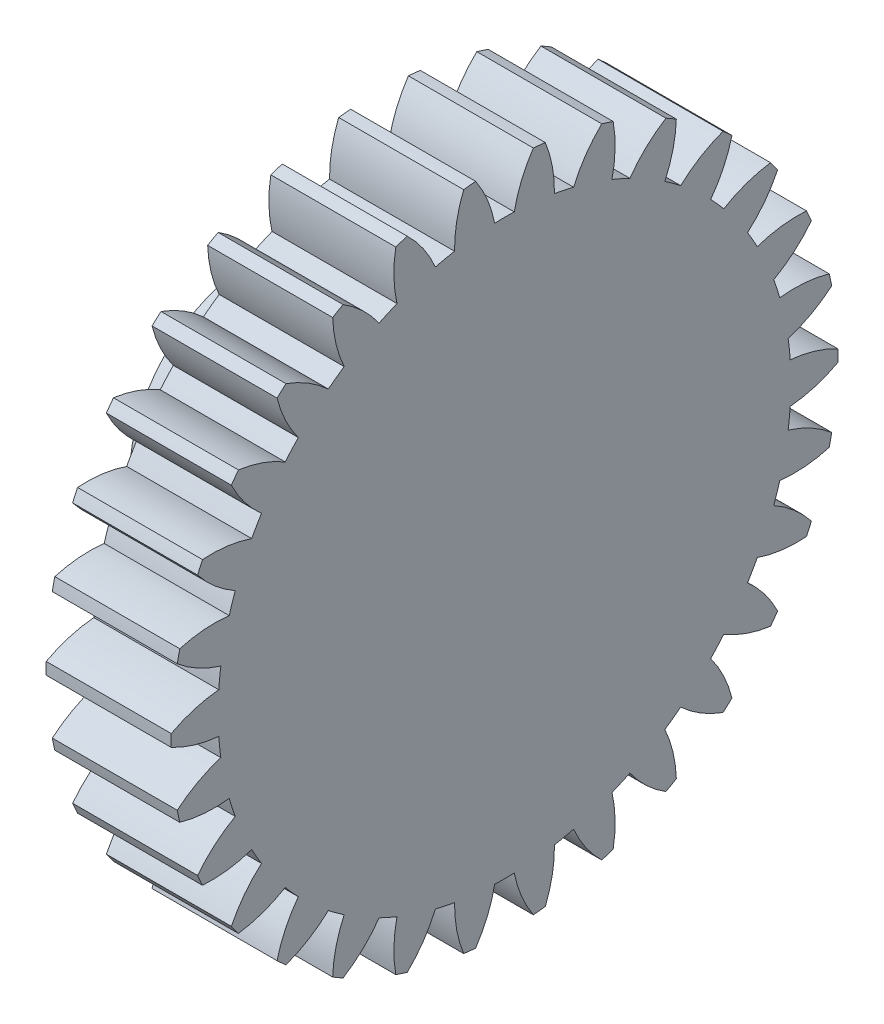
SolidWorks part; units mm, degrees
ref_plane "Plane1" through (0, 0, 0) normal (0, 0, 1) x (1, 0, 0)
ref_plane "Plane2" through (0, 0, 0) normal (0, 1, 0) x (1, 0, 0)
ref_plane "Plane3" through (0, 0, 0) normal (1, 0, 0) x (0, 0, -1)
other "Configuration Table"
sketch "HoldingSke" plane through (0, 0, 0) normal (0, 1, 0) x (1, 0, 0)
  line L0 (0, 0) -> (263.9645, -152.4)
  line L1 (-15, 0) -> (100, 0) construction
  line L2 (0, 0) -> (-2.1039, 2.3779)
  line L3 (0, 0) -> (-11.863, 4.5341)
  line L4 (0, 0) -> (7.479, 4.318)
  line L5 (0, 0) -> (-47.5972, -17.7524)
  line L6 (0, 0) -> (-10.5278, -7.1032)
  line L7 (-2.1039, 2.3779) -> (8.831, 51.988)
  line L8 (-76.2, 54.61) -> (-54.9402, 54.61)
  line L9 (-71.009, 38.7566) -> (-53.1078, 45.2721)
  line L10 (-76.2, 71.12) -> (104.1128, 71.12)
  line L11 (0, 0) -> (-12.7, 0)
  line L12 (-76.2, 101.6) -> (-76.1147, 101.6)
  line L13 (24.9733, 27.94) -> (52.9518, 28.4284)
  line L14 (24.9733, 27.94) -> (24.9746, 27.94)
  line L15 (24.9733, 27.94) -> (100.4006, 29.5858)
  circle A0 centre (0, 0) radius 9.525
  circle A1 centre (0, 0) radius 29.1029
  circle A2 centre (0, 0) radius 38.1
  circle A3 centre (0, 0) radius 9.525
  dimension "MHD" = 58.2058
  dimension "Hub_dia" = 76.2
  dimension "Bore" = 19.05
  dimension "MBD" = 19.05
  dimension "Num_teeth" = 30
  dimension "Pitch" = 304.8
  dimension "Overall_len" = 50.8
  dimension "Show_teeth" = 30
  dimension "Thickness" = 12.7
  dimension "OAL" = 50.801
  dimension "T_dim" = 21.2598
  dimension "Ap" = 20
  dimension "H" = 19.05
  dimension "Pitch_radius" = 180.3128
  dimension "Width" = 12.7
  dimension "Backlash" = 0.0853
  dimension "Addendum_fac" = 1
  dimension "Dedendum_fac" = 1.25
  dimension "Clearance_fac" = 0.25
  dimension "Dedendum_add" = 0.0013
sketch "BasProSke" plane through (0, 0, 0) normal (0, 1, 0) x (1, 0, 0)
  line L0 (-10, 0) -> (60, 0) construction
  line L1 (0, 0) -> (0, 33.8667)
  line L2 (0, 0) -> (12.7, 0)
  line L3 (12.7, 0) -> (12.7, 33.8667)
  line L4 (12.7, 33.8667) -> (0, 33.8667)
  dimension "Thickness" = 12.7
  dimension "Diameter" = 67.7333
revolve "Base-Revolve" add sketch "BasProSke" angle 360 about L0
sketch "TooCutSke" plane through (0, 0, 0) normal (1, 0, 0) x (0, 0, -1)
  line L1 (0, 0) -> (0, 107) construction
  line L2 (0, 0) -> (-1.811, 31.6983) construction
  line L3 (0, 0) -> (-6.63, 63.0805) construction
  line L4 (-1.811, 31.6983) -> (-3.315, 31.5402) construction
  arc A0 (0.9953, 29.0859) -> (-0.9953, 29.0859) centre (0, 0) ccw
  arc A1 (2.9488, 33.7635) -> (-2.9488, 33.7635) centre (0, 0) ccw
  circle A2 centre (0, 0) radius 31.75 construction
  circle A3 centre (0, 0) radius 29.8352 construction
  arc A4 (-0.9953, 29.0859) -> (-2.9488, 33.7635) centre (-13.4553, 26.6289) ccw
  arc A5 (2.9488, 33.7635) -> (0.9953, 29.0859) centre (13.4553, 26.6289) ccw
  dimension "Root_dia" = 58.2058
  dimension "Overcut_dia" = 67.7841
  dimension "Pitch_dia" = 63.5
  dimension "Base_dia" = 59.6705
  dimension "Flank_rad" = 12.7
  dimension "Half_ang" = 6
  dimension "Half_CT" = 1.5123
extrude "ToothCut" cut sketch "TooCutSke" along normal through all
fillet "Breaks" [suppressed] radius 0.0423 tangent propagation no
fillet "RootFillets" [suppressed] radius 0.5304
pattern_circular "TeethCuts" count 30 every 12 about axis through (-10, 0, 0) along (1, 0, 0) of "ToothCut", "RootFillets", "Breaks"
sketch "HubNeaOneSke" plane through (0, 0, 0) normal (-1, 0, 0) x (0, 0, 1)
  circle A0 centre (0, 0) radius 29.1029
  dimension "Diameter" = 58.2058
extrude "HubNearOne" [suppressed] add sketch "HubNeaOneSke" along normal blind 38.101
sketch "HubNeaBotSke" plane through (0, 0, 0) normal (-1, 0, 0) x (0, 0, 1)
  circle A0 centre (0, 0) radius 29.1029
  dimension "Diameter" = 58.2058
extrude "HubNearBoth" [suppressed] add sketch "HubNeaBotSke" along normal blind 19.0505
ref_plane "FarPln" through (12.7, 0, 0) normal (1, 0, 0) x (0, 0, -1)
sketch "HubFarSke" plane through (12.7, 0, 0) normal (1, 0, 0) x (0, 0, -1)
  circle A0 centre (0, 0) radius 29.1029
  dimension "Diameter" = 58.2058
extrude "HubFar" [suppressed] add sketch "HubFarSke" along normal blind 19.0505
sketch "Sketch1" plane through (0, 0, 0) normal (-1, 0, 0) x (0, 0, 1)
  circle A0 centre (0, 0) radius 12.7
  circle A1 centre (0, 0) radius 4.953
  dimension "D1" = 9.906
  dimension "D2" = 25.4
extrude "Boss-Extrude2" add sketch "Sketch1" along normal blind 12.7
sketch "Sketch3" plane through (0, 0, 0) normal (0, 1, 0) x (1, 0, 0)
  line L0 (0, 0.9953) -> (0, -0.9953) construction
  line L2 (-12.7, 0) -> (0, 0) construction
  circle A0 centre (-6.35, 0) radius 3.302
  point P4 (0, 0)
  point P7 (0, 0)
  dimension "D1" = 6.604
  dimension "D2" = 6.35
extrude "Cut-Extrude1" cut sketch "Sketch3" along normal through all
sketch "Sketch4" plane through (0, 0, 0) normal (0, 1, 0) x (1, 0, 0)
  line L1 (-3.527, 4.8895) -> (-9.173, 4.8895)
  line L2 (-9.173, 4.8895) -> (-11.9959, 0)
  line L3 (-11.9959, 0) -> (-9.173, -4.8895)
  line L4 (-9.173, -4.8895) -> (-3.527, -4.8895)
  line L5 (-3.527, -4.8895) -> (-0.7041, 0)
  line L6 (-0.7041, 0) -> (-3.527, 4.8895)
  line L7 (0, 12.7) -> (-12.7, 12.7) construction
  circle A0 centre (-6.35, 0) radius 4.8895 construction
  dimension "D1" = 9.779
extrude "Cut-Extrude2" cut sketch "Sketch4" along normal blind 8.255 contours L3 L4 L5 L6 L1 L2
equation "' \"Pitch@HoldingSke\" = 4"
equation "' \"Num_teeth@HoldingSke\" = 12"
equation "' \"Ap@HoldingSke\" =  20"
equation "' \"Ap@HoldingSke\" = 20"
equation "' \"Width@HoldingSke\" = 0.5"
equation "' \"Hub_dia@HoldingSke\"= 1"
equation "' \"Hub_dia@HoldingSke\" = 1"
equation "' \"Overall_len@HoldingSke\" = 1.0"
equation "' \"Bore@HoldingSke\" = 0.75"
equation "' \"T_dim@HoldingSke\" = 0.85"
equation "' \"Width@KeySke\" = 0.25"
equation "' \"Show_teeth@HoldingSke\" = 13"
equation "' \"Backlash@HoldingSke\" = 0.009"
equation "' \"Addendum_fac@HoldingSke\" = 1.0"
equation "' \"Dedendum_fac@HoldingSke\" = 1.25"
equation "' \"Dedendum_add@HoldingSke\" = 0.00005"
equation "' \"Clearance_fac@HoldingSke\" = 0.25"
equation "' \"Pitch@HoldingSke\" = 0.5"
equation "' \"Num_teeth@HoldingSke\" = 23"
equation "' \"Show_teeth@HoldingSke\" = 23"
equation "' \"Backlash@HoldingSke\" = 0.0375"
equation "\"Overcut_dia@TooCutSke\" = (\"Num_teeth@HoldingSke\" + 2 * \"Addendum_fac@HoldingSke\") / \"Pitch@HoldingSke\" + 0.002"
equation "\"Pitch_dia@TooCutSke\" = \"Num_teeth@HoldingSke\" / \"Pitch@HoldingSke\""
equation "\"Base_dia@TooCutSke\" = \"Num_teeth@HoldingSke\" / \"Pitch@HoldingSke\" * cos((\"Ap@HoldingSke\"  * 3.14159265 / 180))"
equation "\"Root_dia@TooCutSke\" = (\"Num_teeth@HoldingSke\" + 2) / \"Pitch@HoldingSke\" - 2 * (\"Addendum_fac@HoldingSke\" + \"Dedendum_fac@HoldingSke\") / \"Pitch@HoldingSke\" - \"Dedendum_add@HoldingSke\" * 2"
equation "\"Half_ang@TooCutSke\" = 180 / \"Num_teeth@HoldingSke\""
equation "\"Half_CT@TooCutSke\" = \"Num_teeth@HoldingSke\" / \"Pitch@HoldingSke\" * sin((3.14159265 / 2 / \"Num_teeth@HoldingSke\")) / 2 - 7 * \"Backlash@HoldingSke\" / 4"
equation "\"Flank_rad@TooCutSke\" = \"Num_teeth@HoldingSke\" / \"Pitch@HoldingSke\" / 5"
equation "\"Radius@RootFillets\" = \"Clearance_fac@HoldingSke\" / \"Pitch@HoldingSke\" + \"Dedendum_add@HoldingSke\""
equation "\"Break_rad@Breaks\" = 0.02 / \"Pitch@HoldingSke\""
equation "\"Thickness@HoldingSke\" = \"Width@HoldingSke\""
equation "\"OAL@HoldingSke\" = \"Thickness@HoldingSke\""
equation "\"MHD@HoldingSke\" = (\"Num_teeth@HoldingSke\" + 2) / \"Pitch@HoldingSke\" - 2 * (\"Addendum_fac@HoldingSke\" + \"Dedendum_fac@HoldingSke\")  / \"Pitch@HoldingSke\" - \"Dedendum_add@HoldingSke\" * 2"
equation "\"MBD@HoldingSke\" = (\"Num_teeth@HoldingSke\" + 2) / \"Pitch@HoldingSke\" - 2 * (\"Addendum_fac@HoldingSke\" + \"Dedendum_fac@HoldingSke\")  / \"Pitch@HoldingSke\" - \"Dedendum_add@HoldingSke\" * 2 - 0.002"
equation "\"MHD@HoldingSke\" = ((sgn( \"MHD@HoldingSke\" - \"Hub_dia@HoldingSke\" )-1)*( \"MHD@HoldingSke\" - \"Hub_dia@HoldingSke\" ))/-2+ \"Hub_dia@HoldingSke\""
equation "\"MBD@HoldingSke\" = ((sgn( \"MBD@HoldingSke\" - \"Bore@HoldingSke\" )-1)*( \"MBD@HoldingSke\" - \"Bore@HoldingSke\" ))/-2+ \"Bore@HoldingSke\""
equation "\"OAL@HoldingSke\" = ((sgn( \"OAL@HoldingSke\" - \"Overall_len@HoldingSke\" )+1)*( \"OAL@HoldingSke\" - \"Overall_len@HoldingSke\" ))/2 + \"Overall_len@HoldingSke\" + 0.000002"
equation "\"Num_teeth@TeethCuts\" = int( \"Show_teeth@HoldingSke\" ) + 1"
equation "\"Num_teeth@TeethCuts\" = ((sgn( \"Num_teeth@TeethCuts\" - \"Num_teeth@HoldingSke\" )-1)*( \"Num_teeth@TeethCuts\" - \"Num_teeth@HoldingSke\" ))/-2+ \"Num_teeth@HoldingSke\""
equation "\"Num_teeth@TeethCuts\" = ((sgn( \"Num_teeth@TeethCuts\" - 2.0)+1)*( \"Num_teeth@TeethCuts\" - 2.0))/2 +2.0"
equation "\"Angle@TeethCuts\" = 360.0 / \"Num_teeth@HoldingSke\""
equation "\"Diameter@BasProSke\" = (\"Num_teeth@HoldingSke\" + 2 * \"Addendum_fac@HoldingSke\") / \"Pitch@HoldingSke\""
equation "\"Thickness@BasProSke\"  = \"Thickness@HoldingSke\""
equation "' \"Fillet_rad@BasProSke\" =  \"Thickness@HoldingSke\" * 0.05"
equation "' \"Fillet_rad@BasProSke\" = \"Thickness@HoldingSke\" * 0.05"
equation "\"MHD@HoldingSke\" = ((sgn( \"MHD@HoldingSke\" - \"Root_dia@TooCutSke\" )-1)*( \"MHD@HoldingSke\" - \"Root_dia@TooCutSke\" ))/-2+ \"Root_dia@TooCutSke\""
equation "\"Diameter@HubNeaOneSke\" = \"MHD@HoldingSke\""
equation "\"Length@HubNearOne\" = \"OAL@HoldingSke\" - \"Thickness@BasProSke\""
equation "\"Diameter@HubNeaBotSke\" = \"MHD@HoldingSke\""
equation "\"Length@HubNearBoth\" = ( \"OAL@HoldingSke\" - \"Thickness@BasProSke\" ) / 2.0"
equation "\"Thickness@FarPln\" = \"Thickness@BasProSke\""
equation "\"Diameter@HubFarSke\" = \"MHD@HoldingSke\""
equation "\"Length@HubFar\" = ( \"OAL@HoldingSke\" - \"Thickness@BasProSke\" ) / 2.0"
equation "\"Diameter@BorSke\" = \"MBD@HoldingSke\""
equation "\"D1@Bore\" = \"OAL@HoldingSke\" * 2.0"
equation "\"D1@Keyway\" = \"OAL@HoldingSke\" * 2.0"
equation "\"Offset@KeySke\" = \"T_dim@HoldingSke\" - \"MBD@HoldingSke\" / 2.0"
